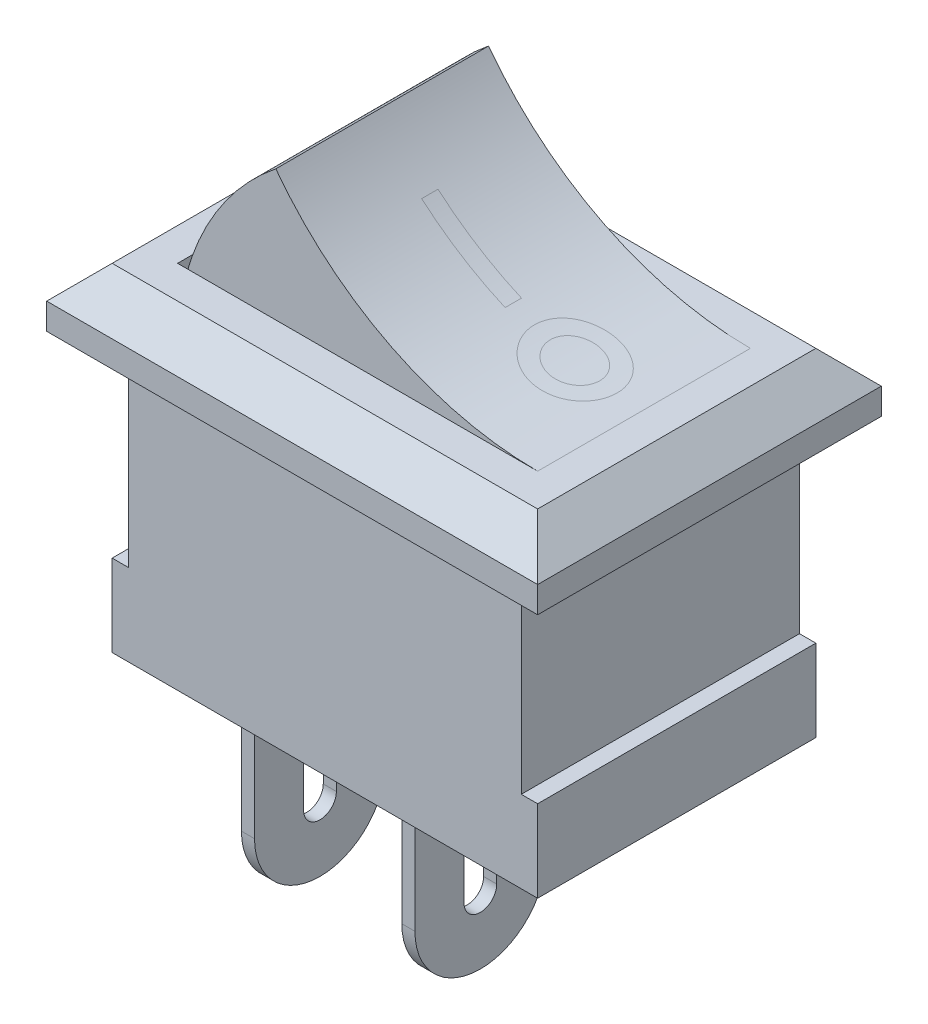
SolidWorks part; units mm, degrees
ref_plane "Alzado" through (0, 0, 0) normal (0, 0, 1) x (1, 0, 0)
ref_plane "Planta" through (0, 0, 0) normal (0, 1, 0) x (1, 0, 0)
ref_plane "Vista lateral" through (0, 0, 0) normal (1, 0, 0) x (0, 0, -1)
sketch "Croquis1" plane through (0, 0, 0) normal (0, 0, 1) x (1, 0, 0)
  line L0 (6, -3) -> (6.5, -3)
  line L1 (-6, 3) -> (6, 3)
  line L2 (-6, 3) -> (-6, -3)
  line L4 (6, 3) -> (6, -3)
  line L5 (-6, 3) -> (6, -3) construction
  line L6 (-6, -3) -> (6, 3) construction
  line L7 (-6.5, -3) -> (-6, -3)
  line L8 (-6.5, -3) -> (-6.5, -5.5)
  line L9 (-6.5, -5.5) -> (6.5, -5.5)
  line L10 (6.5, -3) -> (6.5, -5.5)
  point P0 (0, 0)
  point P11 (0, -5.5)
  dimension "D1" = 12
  dimension "D2" = 8.5
  dimension "D3" = 6
  dimension "D4" = 13
extrude "Saliente-Extruir1" add sketch "Croquis1" along normal mid plane 8.5
sketch "Croquis2" plane through (0, 3, 0) normal (0, 1, 0) x (1, 0, 0)
  line L1 (-7.5, 5.25) -> (7.5, 5.25)
  line L2 (-7.5, 5.25) -> (-7.5, -5.25)
  line L3 (-7.5, -5.25) -> (7.5, -5.25)
  line L4 (7.5, 5.25) -> (7.5, -5.25)
  line L5 (-7.5, 5.25) -> (7.5, -5.25) construction
  line L6 (-7.5, -5.25) -> (7.5, 5.25) construction
  point P0 (0, 0)
  dimension "D1" = 15
  dimension "D2" = 10.5
extrude "Saliente-Extruir2" add sketch "Croquis2" along normal blind 1.8
sketch "Croquis3" plane through (0, 4.8, 0) normal (0, 1, 0) x (1, 0, 0)
  line L1 (-5.5, 3.25) -> (5.5, 3.25)
  line L2 (-5.5, 3.25) -> (-5.5, -3.25)
  line L3 (-5.5, -3.25) -> (5.5, -3.25)
  line L4 (5.5, 3.25) -> (5.5, -3.25)
  line L5 (-5.5, 3.25) -> (5.5, -3.25) construction
  line L6 (-5.5, -3.25) -> (5.5, 3.25) construction
  point P0 (0, 0)
  dimension "D1" = 11
  dimension "D2" = 6.5
extrude "Cortar-Extruir1" cut sketch "Croquis3" against normal blind 1.8
sketch "Croquis4" plane through (0, 0, 0) normal (0, 0, 1) x (1, 0, 0)
  line L0 (5.5, 3) -> (-5.5, 3)
  line L1 (5.5, 3) -> (5.5, 4.8)
  line L2 (-7.5, 4.8) -> (7.5, 4.8) construction
  arc A0 (5.5, 4.8) -> (-2.5, 8.8) centre (5.5, 14.8) cw
  arc A1 (-5.5, 3) -> (-2.5, 8.8) centre (2.487, 2.5446) cw
  dimension "D1" = 8
  dimension "D2" = 10
  dimension "D3" = 8
extrude "Saliente-Extruir3" add sketch "Croquis4" along normal up to surface and the other way up to surface separate body up to face at (0, 3.9, 3.25) other way up to face at (0, 3.9, -3.25)
sketch "Croquis5" plane through (0, 0, 0) normal (0, 0, 1) x (1, 0, 0)
  line L0 (-2.5, 8.8) -> (5.5, 4.8) construction
  line L1 (-7.5, 4.8) -> (7.5, 4.8) construction
ref_plane "Plano1" through (3.02, 6.04, 0) normal (-0.4472, -0.8944, 0) x (0.8944, -0.4472, 0)
sketch "Croquis6" plane through (3.02, 6.04, 0) normal (-0.4472, -0.8944, 0) x (0.8944, -0.4472, 0)
  line L0 (-6.1715, 0) -> (2.7727, 0) construction
  line L1 (-1.1715, 0.25) -> (-4.1715, 0.25)
  line L2 (-1.1715, 0.25) -> (-1.1715, -0.25)
  line L3 (-1.1715, -0.25) -> (-4.1715, -0.25)
  line L4 (-4.1715, 0.25) -> (-4.1715, -0.25)
  line L5 (-1.1715, 0.25) -> (-4.1715, -0.25) construction
  line L6 (-1.1715, -0.25) -> (-4.1715, 0.25) construction
  line L7 (-6.1715, 3.25) -> (-6.1715, -3.25) construction
  line L8 (2.7727, 3.25) -> (2.7727, -3.25) construction
  circle A0 centre (0.7727, 0) radius 1.25
  circle A1 centre (0.7727, 0) radius 0.75
  point P0 (-2.6715, 0)
  dimension "D4" = 2.5
  dimension "D1" = 3
  dimension "D2" = 0.5
  dimension "D3" = 2
  dimension "D6" = 2
  dimension "D5" = 0.5
split line "Línea de partición1"
sketch "Croquis7" plane through (0, 0, 0) normal (0, 0, 1) x (1, 0, 0)
  line L0 (-6.5, -5.5) -> (6.5, -5.5) construction
  line L1 (0.1, -5.5) -> (0.5, -5.5)
  line L2 (0.1, -5.5) -> (0.1, -12.5)
  line L3 (0.1, -12.5) -> (0.5, -12.5)
  line L4 (0.5, -5.5) -> (0.5, -12.5)
  line L5 (6.5, -5.5) -> (6.5, -3) construction
  line L6 (-2.15, -5.5) -> (-2.15, -12.5) construction
  line L7 (-4.8, -5.5) -> (-4.8, -12.5)
  line L8 (-4.4, -12.5) -> (-4.8, -12.5)
  line L9 (-4.4, -5.5) -> (-4.4, -12.5)
  line L10 (-4.4, -5.5) -> (-4.8, -5.5)
  dimension "D1" = 6
  dimension "D2" = 7
  dimension "D3" = 0.4
  dimension "D4" = 4.5
extrude "Saliente-Extruir4" add sketch "Croquis7" along normal mid plane 4 separate body
fillet "Redondeo1" radius 2 2 edges at (-4.6, -12.5, -2) (-4.6, -12.5, 2)
fillet "Redondeo2" radius 2 2 edges at (0.3, -12.5, -2) (0.3, -12.5, 2)
sketch "Croquis9" plane through (0.5, 0, 0) normal (1, 0, 0) x (0, 0, -1)
  line L0 (-0.75, -12.5) -> (0.75, -12.5) construction
  line L1 (2, -10.5) -> (2, -5.5) construction
  line L2 (0, -10.5) -> (0, -7.5) construction
  line L3 (-0.5, -10.5) -> (-0.5, -7.5)
  line L4 (0.5, -10.5) -> (0.5, -7.5)
  circle A0 centre (0, -10.5) radius 0.5 construction
  arc A1 (-0.5, -10.5) -> (0.5, -10.5) centre (0, -10.5) ccw
  arc A2 (0.5, -7.5) -> (-0.5, -7.5) centre (0, -7.5) ccw
  point P9 (0, -9)
  dimension "D1" = 1
  dimension "D2" = 2
  dimension "D3" = 2
  dimension "D4" = 3
extrude "Cortar-Extruir2" cut sketch "Croquis9" against normal through all
sketch "Croquis10" plane through (0, 0, 0) normal (0, 0, 1) x (1, 0, 0)
  line L1 (-7.5, 3) -> (7.5, 3) construction
  line L9 (-6.5, -5.5) -> (6.5, -5.5)
  line L10 (-6.5, -5.5) -> (-6.5, 3)
  line L11 (-6.5, 3) -> (6.5, 3)
  line L12 (6.5, -5.5) -> (6.5, 3)
  dimension "D1" = 8.5
  dimension "D2" = 13
chamfer "Chaflán1" distance 1 angle 45 4 edges at (-7.5, 4.8, 0) (0, 4.8, -5.25) (7.5, 4.8, 0) (0, 4.8, 5.25)
sketch "Croquis11" plane through (0, 0, 0) normal (0, 0, 1) x (1, 0, 0)
  line L0 (-6.5, -5.5) -> (-6.5, 3)
  line L1 (-7.5, 3) -> (7.5, 3) construction
  line L2 (-6.5, 3) -> (6.5, 3)
  line L3 (6.5, 3) -> (6.5, -7)
  line L5 (-6.5, -5.5) -> (-6.5, -13)
  line L6 (-6.5, -13) -> (1.5, -13)
  line L7 (1.5, -13) -> (1.5, -7)
  line L9 (1.5, -7) -> (6.5, -7)
  dimension "D1" = 5
  dimension "D2" = 8
  dimension "D3" = 16
  dimension "D4" = 13
  dimension "D5" = 10
